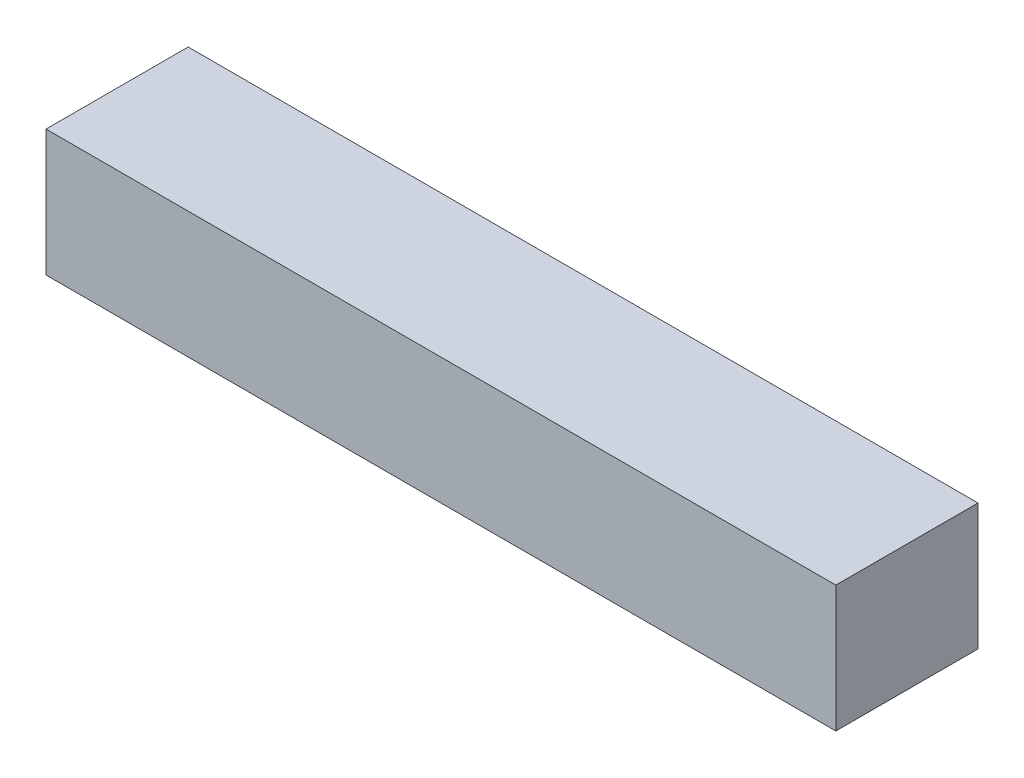
SolidWorks part; units mm, degrees
ref_plane "Front Plane" through (0, 0, 0) normal (0, 0, 1) x (1, 0, 0)
ref_plane "Top Plane" through (0, 0, 0) normal (0, 1, 0) x (1, 0, 0)
ref_plane "Right Plane" through (0, 0, 0) normal (1, 0, 0) x (0, 0, -1)
other "Configuration Table"
sketch "Sketch1" plane through (0, 0, 0) normal (1, 0, 0) x (0, 0, -1)
  line L1 (-34.5, 176) -> (-39, 176)
  line L2 (-34.5, 176) -> (-34.5, 180)
  line L3 (-34.5, 180) -> (-39, 180)
  line L4 (-39, 176) -> (-39, 180)
  line L5 (-34.5, 176) -> (-39, 180) construction
  line L6 (-34.5, 180) -> (-39, 176) construction
  point P0 (-36.75, 178)
extrude "crosshead" add sketch "Sketch1" along normal blind 25 from offset 54 separate body
sketch "Sketch2" plane through (0, 0, 0) normal (1, 0, 0) x (0, 0, -1)
  line L1 (-35.4, 175.9) -> (-37.6, 175.9)
  line L2 (-35.4, 175.9) -> (-35.4, 177.5)
  line L3 (-35.4, 177.5) -> (-37.6, 177.5)
  line L4 (-37.6, 175.9) -> (-37.6, 177.5)
  line L5 (-35.4, 175.9) -> (-37.6, 177.5) construction
  line L6 (-35.4, 177.5) -> (-37.6, 175.9) construction
  point P0 (-36.5, 176.7)
extrude "rod_slot" add sketch "Sketch2" along normal blind 6.2 from offset 63.24 separate body
combine bodies "Combine1" operation type subtract main body 102 bodies to subtract 103
